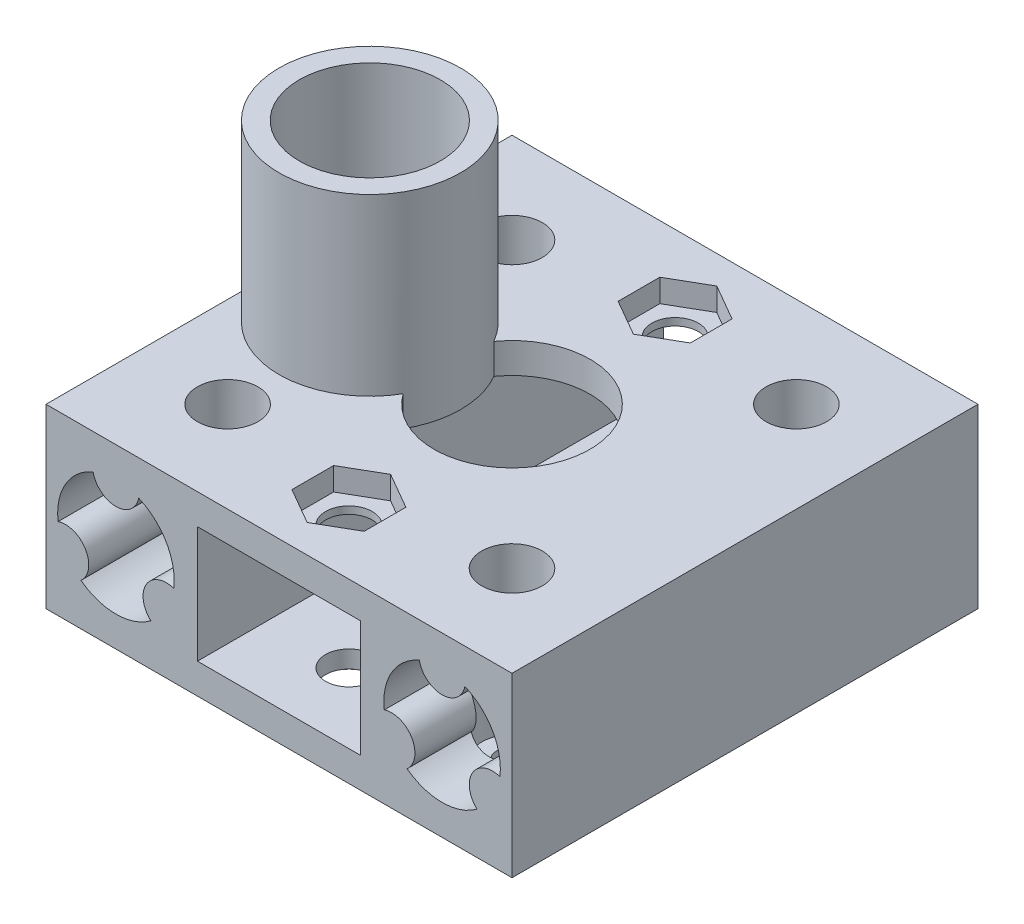
SolidWorks part; units mm, degrees
ref_plane "Front Plane" through (0, 0, 0) normal (0, 0, 1) x (1, 0, 0)
ref_plane "Top Plane" through (0, 0, 0) normal (0, 1, 0) x (1, 0, 0)
ref_plane "Right Plane" through (0, 0, 0) normal (1, 0, 0) x (0, 0, -1)
sketch "Sketch1" plane through (0, 0, 0) normal (0, 0, 1) x (1, 0, 0)
  line L0 (17.78, 0) -> (-17.78, 0)
  line L1 (25.4, -9.652) -> (-25.4, -9.652)
  line L2 (25.4, -9.652) -> (25.4, 9.652)
  line L3 (25.4, 9.652) -> (-25.4, 9.652)
  line L4 (-25.4, -9.652) -> (-25.4, 9.652)
  line L5 (25.4, -9.652) -> (-25.4, 9.652) construction
  line L6 (25.4, 9.652) -> (-25.4, -9.652) construction
  line L7 (-25.4, -9.652) -> (-25.4, -1.531)
  line L8 (-25.4, -1.7771) -> (-25.4, -4.5729)
  line L9 (25.4, -1.7771) -> (25.4, -4.5729)
  circle A0 centre (-17.78, 0) radius 3.81
  circle A1 centre (17.78, 0) radius 3.81
  circle A2 centre (-17.78, 0) radius 6.35
  circle A3 centre (17.78, 0) radius 6.35
  circle A4 centre (-17.78, 6.35) radius 2.54
  circle A5 centre (17.78, 6.35) radius 2.54
  circle A6 centre (-12.2807, -3.175) radius 2.54
  arc A7 (-25.4, -4.5729) -> (-25.4, -1.7771) centre (-23.2793, -3.175) ccw
  arc A8 (25.4, -1.7771) -> (25.4, -4.5729) centre (23.2793, -3.175) ccw
  circle A9 centre (12.2807, -3.175) radius 2.54
  point P0 (0, 0)
  point P9 (0, 0)
  point P24 (-25.4, -9.652)
  dimension "D4" = 12.7
  dimension "D5" = 7.62
  dimension "D6" = 7.62
  dimension "D7" = 12.7
  dimension "D1" = 50.8
  dimension "D2" = 19.304
  dimension "D3" = 35.56
  dimension "D8" = 3
  dimension "D9" = 3
extrude "Boss-Extrude1" add sketch "Sketch1" along normal blind 50.8 contours L2 L1 L4 L3
extrude "Cut-Extrude1" cut sketch "Sketch1<3>" along normal through all contours A2 | A3
sketch "Sketch1<3>" plane through (0, 0, 0) normal (0, 0, 1) x (1, 0, 0) same geometry as "Sketch1"
extrude "Boss-Extrude2" add sketch "Sketch1<4>" along normal blind 50.8 contours A4 | A7 L8 | A6 | A5 | A8 L9 | A9
sketch "Sketch1<4>" plane through (0, 0, 0) normal (0, 0, 1) x (1, 0, 0) same geometry as "Sketch1"
sketch "Sketch2" plane through (0, -9.652, 0) normal (0, -1, 0) x (1, 0, 0)
  line L0 (-25.4, 50.8) -> (25.4, 0) construction
  line L1 (25.4, 50.8) -> (-25.4, 0) construction
  line L3 (15.5, 9.9) -> (-15.5, 9.9)
  line L4 (15.5, 9.9) -> (15.5, 40.9)
  line L5 (15.5, 40.9) -> (-15.5, 40.9)
  line L6 (-15.5, 9.9) -> (-15.5, 40.9)
  line L7 (15.5, 9.9) -> (-15.5, 40.9) construction
  line L8 (15.5, 40.9) -> (-15.5, 9.9) construction
  circle A0 centre (0, 25.4) radius 8.509
  circle A1 centre (0, 25.4) radius 11.049
  circle A2 centre (-15.5, 40.9) radius 1.651
  circle A3 centre (-15.5, 9.9) radius 1.651
  circle A4 centre (15.5, 9.9) radius 1.651
  circle A5 centre (15.5, 40.9) radius 1.651
  dimension "D1" = 17.018
  dimension "D2" = 22.098
  dimension "D5" = 3.302
  dimension "D6" = 3.302
  dimension "D7" = 3.302
  dimension "D8" = 3.302
  dimension "D3" = 31
  dimension "D4" = 31
extrude "Cut-Extrude2" cut sketch "Sketch2" against normal blind 2.54 contours A1
extrude "Cut-Extrude3" cut sketch "Sketch2<3>" against normal through all contours A2 | A0 | A3 | A4 | A5
sketch "Sketch2<3>" plane through (0, -9.652, 0) normal (0, -1, 0) x (1, 0, 0) same geometry as "Sketch2"
sketch "Sketch3" plane through (0, 9.652, 0) normal (0, 1, 0) x (1, 0, 0)
  circle A0 centre (-15.5, -9.9) radius 3.302
  circle A1 centre (15.5, -9.9) radius 3.302
  circle A2 centre (15.5, -40.9) radius 3.302
  circle A3 centre (-15.5, -40.9) radius 3.302
  dimension "D1" = 6.604
  dimension "D2" = 6.604
  dimension "D3" = 6.604
  dimension "D4" = 6.604
extrude "Cut-Extrude4" cut sketch "Sketch3" against normal offset from surface (18.034 mm away) 1.27 up to face at (17.151, -9.652, 40.9)
sketch "Sketch4" plane through (0, 0, 0) normal (0, 0, -1) x (-1, 0, 0)
  line L1 (8.89, 6.35) -> (-8.89, 6.35)
  line L2 (8.89, 6.35) -> (8.89, -6.35)
  line L3 (8.89, -6.35) -> (-8.89, -6.35)
  line L4 (-8.89, 6.35) -> (-8.89, -6.35)
  line L5 (8.89, 6.35) -> (-8.89, -6.35) construction
  line L6 (8.89, -6.35) -> (-8.89, 6.35) construction
  point P0 (0, 0)
  dimension "D1" = 17.78
  dimension "D2" = 12.7
extrude "Cut-Extrude5" cut sketch "Sketch4" against normal through all
sketch "Sketch5" plane through (0, -9.652, 0) normal (0, -1, 0) x (1, 0, 0)
  line L0 (0, 25.4) -> (0, 43.18) construction
  line L1 (0, 25.4) -> (0, 7.62) construction
  line L3 (0, 38.6339) -> (3.937, 40.907)
  line L4 (3.937, 40.907) -> (3.937, 45.453)
  line L5 (3.937, 45.453) -> (0, 47.7261)
  line L6 (0, 47.7261) -> (-3.937, 45.453)
  line L7 (-3.937, 45.453) -> (-3.937, 40.907)
  line L8 (-3.937, 40.907) -> (0, 38.6339)
  line L9 (0, 12.1661) -> (-3.937, 9.893)
  line L10 (-3.937, 9.893) -> (-3.937, 5.347)
  line L11 (-3.937, 5.347) -> (0, 3.0739)
  line L12 (0, 3.0739) -> (3.937, 5.347)
  line L13 (3.937, 5.347) -> (3.937, 9.893)
  line L14 (3.937, 9.893) -> (0, 12.1661)
  circle A0 centre (0, 43.18) radius 3.937 construction
  circle A1 centre (0, 7.62) radius 3.937 construction
  circle A2 centre (0, 43.18) radius 2.54
  circle A3 centre (0, 7.62) radius 2.54
  dimension "D5" = 5.08
  dimension "D6" = 5.08
  dimension "D1" = 17.78
  dimension "D2" = 17.78
  dimension "D3" = 7.874
  dimension "D4" = 7.874
extrude "Cut-Extrude6" cut sketch "Sketch5" against normal through all contours A2 | A3
sketch "Sketch6" plane through (0, 9.652, 0) normal (0, 1, 0) x (1, 0, 0)
  line L1 (0, -3.0739) -> (-3.937, -5.347)
  line L2 (-3.937, -5.347) -> (-3.937, -9.893)
  line L3 (-3.937, -9.893) -> (0, -12.1661)
  line L4 (0, -12.1661) -> (3.937, -9.893)
  line L5 (3.937, -9.893) -> (3.937, -5.347)
  line L6 (3.937, -5.347) -> (0, -3.0739)
  line L7 (0, -38.6339) -> (-3.937, -40.907)
  line L8 (-3.937, -40.907) -> (-3.937, -45.453)
  line L9 (-3.937, -45.453) -> (0, -47.7261)
  line L10 (0, -47.7261) -> (3.937, -45.453)
  line L11 (3.937, -45.453) -> (3.937, -40.907)
  line L12 (3.937, -40.907) -> (0, -38.6339)
  circle A0 centre (0, -7.62) radius 3.937 construction
  circle A1 centre (0, -43.18) radius 3.937 construction
  dimension "D1" = 7.874
  dimension "D2" = 7.874
extrude "Cut-Extrude7" cut sketch "Sketch6" against normal blind 2.5 contours L4 L5 L6 L1 L2 L3 | L12 L7 L8 L9 L10 L11
sketch "Sketch7" plane through (0, -9.652, 0) normal (0, -1, 0) x (1, 0, 0)
  circle A0 centre (0, 43.18) radius 4.5
  circle A1 centre (0, 7.62) radius 4.5
  dimension "D1" = 9
  dimension "D2" = 9
extrude "Cut-Extrude8" cut sketch "Sketch7" against normal blind 1.397 contours A1 | A0
sketch "Sketch10" plane through (0, 9.652, 0) normal (0, 1, 0) x (1, 0, 0)
  line L0 (0, -25.4) -> (-15.5, -25.4)
  line L1 (-15.5, -9.9) -> (-15.5, -40.9) construction
  circle A0 centre (-15.5, -25.4) radius 7.6835
  circle A2 centre (-15.5, -25.4) radius 9.9
  dimension "D1" = 15.367
extrude "Boss-Extrude3" add sketch "Sketch10" against normal blind 3.302 contours A0
extrude "Boss-Extrude4" add sketch "Sketch10<3>" against normal blind 3.302 contours A2
sketch "Sketch10<3>" plane through (0, 9.652, 0) normal (0, 1, 0) x (1, 0, 0) same geometry as "Sketch10"
extrude "Boss-Extrude5" add sketch "Sketch10<5>" along normal blind 19.05 contours A0 | A2
sketch "Sketch10<5>" plane through (0, 9.652, 0) normal (0, 1, 0) x (1, 0, 0) same geometry as "Sketch10"
